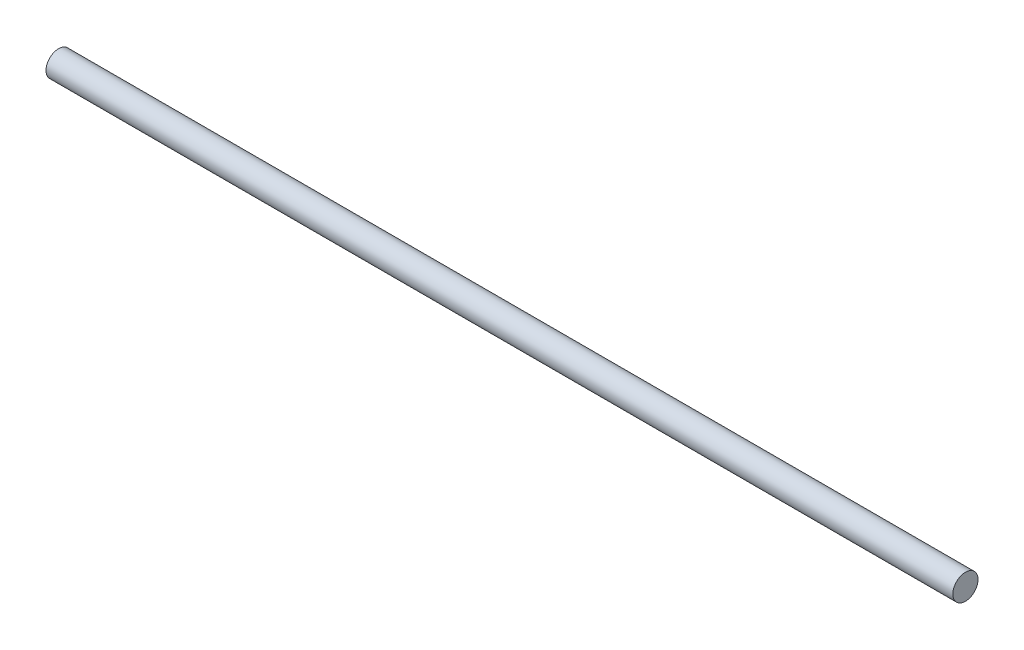
SolidWorks part; units mm, degrees
ref_plane "前基準面" through (0, 0, 0) normal (0, 0, 1) x (1, 0, 0)
ref_plane "上基準面" through (0, 0, 0) normal (0, 1, 0) x (1, 0, 0)
ref_plane "右基準面" through (0, 0, 0) normal (1, 0, 0) x (0, 0, -1)
ref_axis "基準軸1" through (0, -55, 0) along (0, 1, 0)
ref_axis "基準軸2" through (-88.99, 0, 0) along (1, 0, 0)
ref_axis "基準軸3" through (0, 0, 55) along (0, 0, -1)
sketch "草圖2" plane through (0, 0, 0) normal (1, 0, 0) x (0, 0, -1)
  line L1 (55, 0) -> (-55, 0) construction
  line L2 (0, -55) -> (0, 55) construction
  circle A0 centre (0, 18) radius 2.5
  dimension "D1" = 5
  dimension "D2" = 18
extrude "填料-伸長2" add sketch "草圖2" along normal blind 180 separate body
ref_plane "平面1" through (-80, 0, 0) normal (1, 0, 0) x (0, 0, -1)
